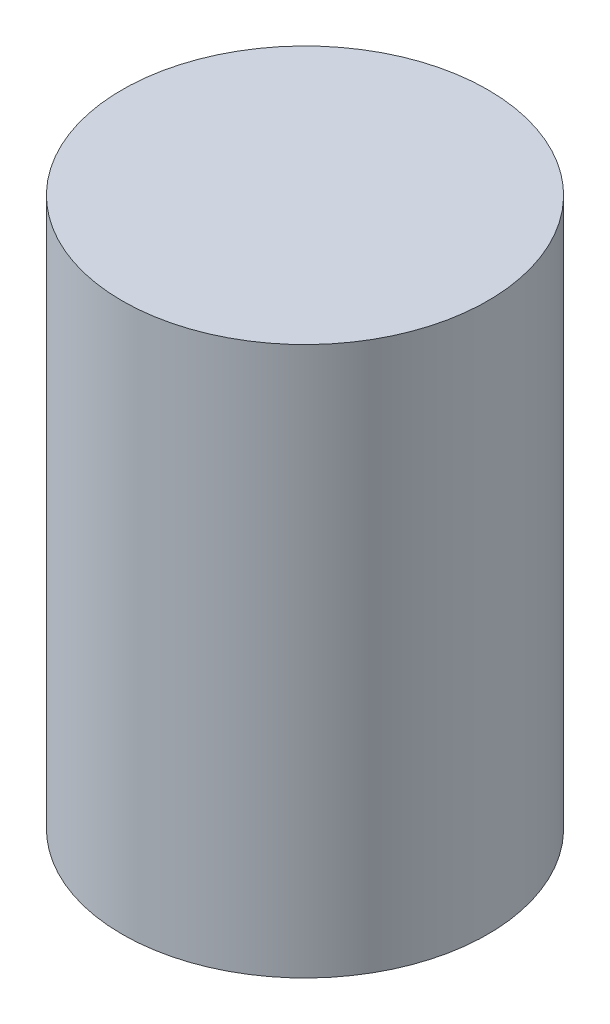
SolidWorks part; units mm, degrees
ref_plane "Front Plane" through (0, 0, 0) normal (0, 0, 1) x (1, 0, 0)
ref_plane "Top Plane" through (0, 0, 0) normal (0, 1, 0) x (1, 0, 0)
ref_plane "Right Plane" through (0, 0, 0) normal (1, 0, 0) x (0, 0, -1)
sketch "Sketch1" plane through (0, 0, 0) normal (0, 1, 0) x (1, 0, 0)
  circle A0 centre (-17.4188, 18.5985) radius 60
extrude "Boss-Extrude1" add sketch "Sketch1" along normal blind 180
ref_point "wrist point"
ref_axis "wrist+front" through (-17.4188, 180, -18.5985) along (0, 0, 1)
ref_axis "wrist+right" through (-17.4188, 180, -18.5985) along (1, 0, 0)
ref_axis "wrist+top" through (-17.4188, 180, -18.5985) along (0, 1, 0)
